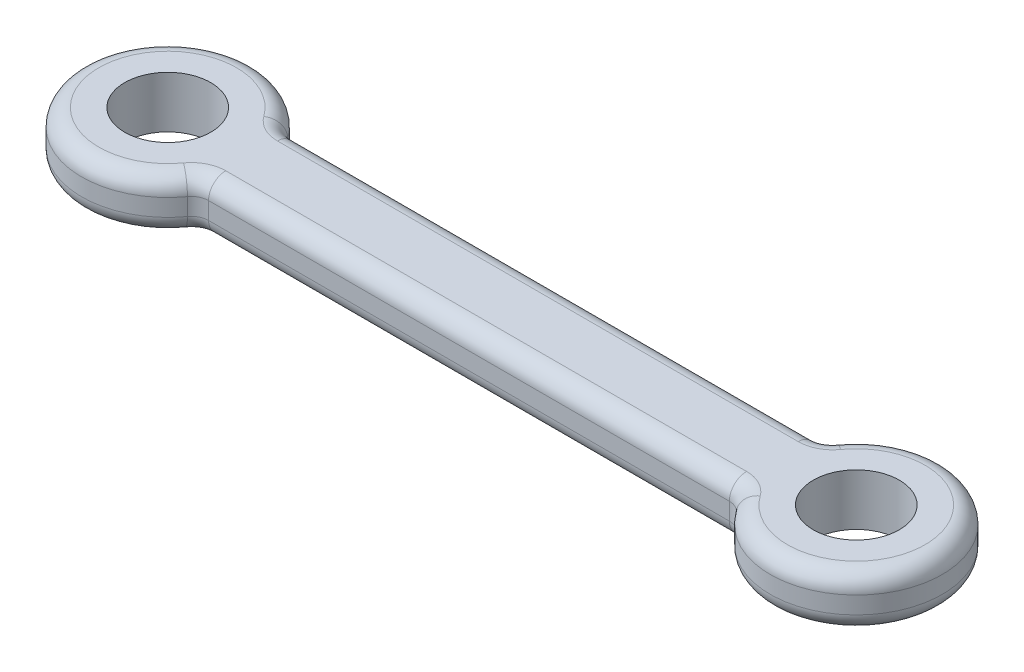
SolidWorks part; units mm, degrees
ref_plane "Plano frontal" through (0, 0, 0) normal (0, 0, 1) x (1, 0, 0)
ref_plane "Plano superior" through (0, 0, 0) normal (0, 1, 0) x (1, 0, 0)
ref_plane "Plano direito" through (0, 0, 0) normal (1, 0, 0) x (0, 0, -1)
sketch "Esboço1" plane through (0, 0, 0) normal (0, 1, 0) x (1, 0, 0)
  line L2 (21.6506, 12.5) -> (178.3494, 12.5)
  line L3 (21.6506, -12.5) -> (178.3494, -12.5)
  circle A0 centre (0, 0) radius 12.5
  circle A2 centre (200, 0) radius 12.5
  arc A4 (21.6506, 12.5) -> (21.6506, -12.5) centre (0, 0) ccw
  arc A5 (178.3494, -12.5) -> (178.3494, 12.5) centre (200, 0) ccw
  point P11 (0, 0)
  point P12 (0, 0)
  dimension "D1" = 25
  dimension "D2" = 50
  dimension "D3" = 50
  dimension "D4" = 25
extrude "Ressalto-extrusão1" add sketch "Esboço1" along normal blind 15
fillet "Filete1" radius 5 12 edges at (-25, 15, 0) (-25, 0, 0) (21.6506, 7.5, 12.5) (100, 15, 12.5) (100, 0, 12.5) (178.3494, 7.5, 12.5) (225, 15, 0) (225, 0, 0) (178.3494, 7.5, -12.5) (100, 15, -12.5) (21.6506, 7.5, -12.5) (100, 0, -12.5)
